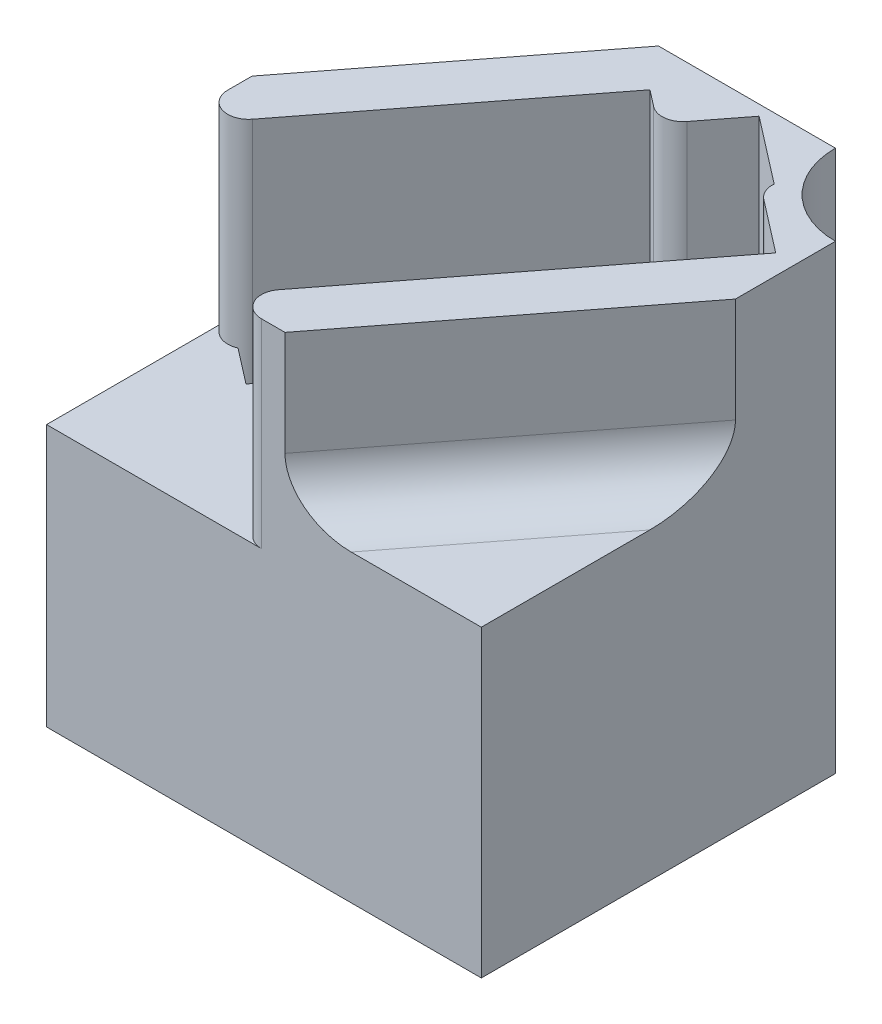
SolidWorks part; units mm, degrees
ref_plane "Front Plane" through (0, 0, 0) normal (0, 0, 1) x (1, 0, 0)
ref_plane "Top Plane" through (0, 0, 0) normal (0, 1, 0) x (1, 0, 0)
ref_plane "Right Plane" through (0, 0, 0) normal (1, 0, 0) x (0, 0, -1)
sketch "Sketch1" plane through (0, 0, 0) normal (0, 1, 0) x (1, 0, 0)
  line L0 (33.8, 41.5) -> (41.5, 41.5) construction
  line L1 (0, 0) -> (41.5, 0) construction
  line L2 (0, 0) -> (0, 41.5) construction
  line L3 (0, 41.5) -> (33.8, 41.5) construction
  line L4 (41.5, 0) -> (41.5, 33.8) construction
  line L5 (33.8, 41.5) -> (0, 41.5)
  line L6 (41.5, 33.8) -> (41.5, 0)
  line L7 (41.5, 0) -> (0, 0)
  line L8 (0, 41.5) -> (0, 0)
  line L9 (41.5, 41.5) -> (41.5, 33.8) construction
  arc A0 (33.8, 41.5) -> (41.5, 33.8) centre (41.5, 41.5) ccw
  point P8 (20.75, 0)
  dimension "D4" = 15.4
  dimension "D1" = 41.5
  dimension "D2" = 0
  dimension "D3" = 0
extrude "Boss-Extrude1" add sketch "Sketch1" along normal blind 44
sketch "Sketch2" plane through (0, 44, 0) normal (0, 1, 0) x (1, 0, 0)
  line L0 (6.3304, 0) -> (33.8446, 35.6086) construction
  line L1 (0, 0) -> (41.5, 0) construction
  line L2 (33.8446, 35.6086) -> (27.5141, 40.5) construction
  line L3 (27.5141, 40.5) -> (0, 4.8914) construction
  line L4 (0, 4.8914) -> (6.3304, 0) construction
  line L5 (0, 41.5) -> (0, 0) construction
  line L6 (6.3304, 0) -> (0, 0)
  line L7 (0, 0) -> (0, 4.8914)
  line L8 (0, 4.8914) -> (27.5141, 40.5)
  line L9 (27.5141, 40.5) -> (33.8446, 35.6086)
  line L10 (33.8446, 35.6086) -> (6.3304, 0)
  line L12 (33.8, 41.5) -> (0, 41.5) construction
  point P6 (36.4794, 32.8339)
  point P9 (27.8358, 40.3063)
  dimension "D1" = 8
  dimension "D2" = 45
  dimension "D3" = 1
extrude "Cut-Extrude1" cut sketch "Sketch2" against normal blind 19
sketch "Sketch3" plane through (0, 44, 0) normal (0, 1, 0) x (1, 0, 0)
  line L0 (6.1652, 12.8704) -> (23.2851, 35.0268)
  line L1 (6.1652, 12.8704) -> (3, 15.3161)
  line L2 (23.2851, 35.0268) -> (20.1199, 37.4725)
  line L3 (3, 15.3161) -> (20.1199, 37.4725)
  line L4 (27.5141, 40.5) -> (0, 4.8914) construction
  line L8 (0, 41.5) -> (0, 4.8914) construction
  point P8 (15.3108, 17.697)
  dimension "D1" = 4
  dimension "D2" = 28
  dimension "D3" = 3
extrude "Cut-Extrude2" cut sketch "Sketch3" against normal blind 22
sketch "Sketch5" plane through (0, 44, 0) normal (0, 1, 0) x (1, 0, 0)
  line L0 (11.2689, 6.3914) -> (33.2803, 34.8783)
  line L1 (11.2689, 6.3914) -> (17.5994, 1.5)
  line L2 (33.2803, 34.8783) -> (39.6107, 29.9869)
  line L3 (17.5994, 1.5) -> (39.6107, 29.9869)
  line L4 (6.3304, 0) -> (33.8446, 35.6086) construction
  line L5 (6.3304, 0) -> (41.5, 0) construction
  dimension "D1" = 8
  dimension "D2" = 36
  dimension "D3" = 1.5
extrude "Cut-Extrude3" cut sketch "Sketch5" against normal blind 19
sketch "Sketch6" plane through (0, 44, 0) normal (0, 1, 0) x (1, 0, 0)
  line L0 (17.5994, 1.5) -> (16.4403, 0)
  line L1 (6.3304, 0) -> (41.5, 0) construction
  line L2 (16.4403, 0) -> (0, 0)
  line L3 (0, 0) -> (0, 11.4335)
  line L4 (0, 41.5) -> (0, 4.8914) construction
  line L5 (0, 11.4335) -> (3, 15.3161)
  line L6 (3, 15.3161) -> (6.1652, 12.8704)
  line L7 (6.1652, 12.8704) -> (11.2689, 6.3914)
  line L8 (11.2689, 6.3914) -> (17.5994, 1.5) construction
  line L9 (11.2689, 6.3914) -> (17.5994, 1.5)
  line L10 (17.5994, 1.5) -> (39.6107, 29.9869) construction
  line L11 (20.1199, 37.4725) -> (3, 15.3161) construction
  point P21 (8.7519, 8.3363)
extrude "Cut-Extrude4" cut sketch "Sketch6" against normal up to surface (19 mm away) up to face at (18.0817, 25, -18.3322)
sketch "Sketch7" plane through (0, 44, 0) normal (0, 1, 0) x (1, 0, 0)
  line L0 (22.759, 0) -> (41.5, 24.2544)
  line L1 (16.4403, 0) -> (41.5, 0) construction
  line L2 (41.5, 0) -> (41.5, 33.8) construction
  line L3 (41.5, 24.2544) -> (41.5, 0)
  line L4 (41.5, 0) -> (22.759, 0)
  line L5 (0, 19.6111) -> (16.9132, 41.5)
  line L6 (0, 41.5) -> (0, 11.4335) construction
  line L7 (33.8, 41.5) -> (0, 41.5) construction
  line L8 (16.9132, 41.5) -> (0, 41.5)
  line L9 (0, 41.5) -> (0, 19.6111)
  line L10 (20.1199, 37.4725) -> (0, 11.4335) construction
  line L11 (16.4403, 0) -> (39.6107, 29.9869) construction
  dimension "D1" = 5
  dimension "D2" = 5
extrude "Cut-Extrude5" cut sketch "Sketch7" against normal blind 15
fillet "Fillet1" radius 2 4 edges at (33.2803, 34.5, -34.8783) (23.2851, 34.5, -35.0268) (16.4403, 34.5, 0) (0, 34.5, -11.4335)
fillet "Fillet2" radius 5 2 edges at (8.4566, 29, -30.5556) (32.1295, 29, -12.1272)
